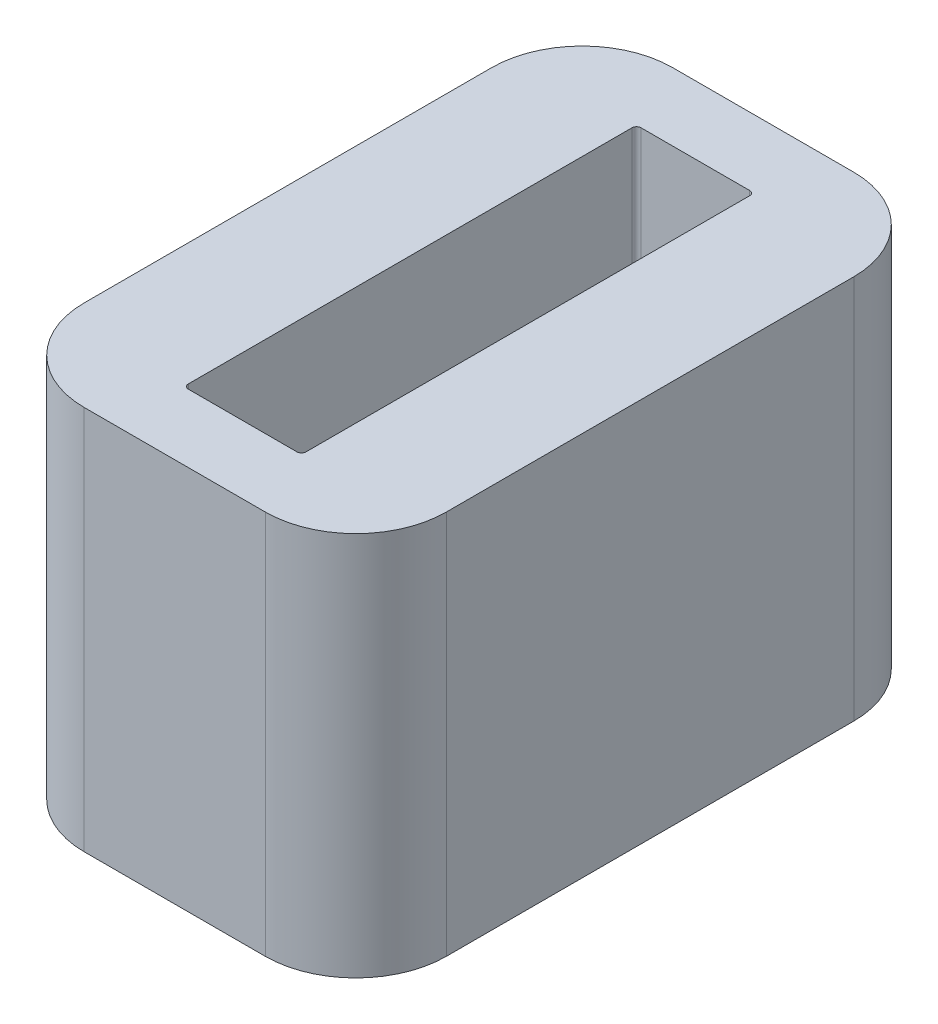
SolidWorks part; units mm, degrees
material "Copper"
ref_plane "Front Plane" through (0, 0, 0) normal (0, 0, 1) x (1, 0, 0)
ref_plane "Top Plane" through (0, 0, 0) normal (0, 1, 0) x (1, 0, 0)
ref_plane "Right Plane" through (0, 0, 0) normal (1, 0, 0) x (0, 0, -1)
sketch "Sketch1" plane through (0, 97.2795, 0) normal (0, 1, 0) x (1, 0, 0)
  line L0 (92.0978, 84.0094) -> (86.0478, 74.2094) construction
  line L1 (86.0478, 74.2094) -> (92.0978, 74.2094) construction
  line L2 (86.0478, 74.2094) -> (86.0478, 84.0094) construction
  line L3 (86.0478, 84.0094) -> (92.0978, 84.0094) construction
  line L4 (92.0978, 74.2094) -> (92.0978, 84.0094) construction
  line L6 (87.0728, 72.6094) -> (91.0728, 72.6094)
  line L7 (85.0728, 74.6094) -> (85.0728, 83.6094)
  line L8 (87.0728, 85.6094) -> (91.0728, 85.6094)
  line L9 (93.0728, 74.6094) -> (93.0728, 83.6094)
  line L10 (85.0728, 72.6094) -> (93.0728, 85.6094) construction
  line L11 (85.0728, 85.6094) -> (93.0728, 72.6094) construction
  line L12 (87.7728, 74.1094) -> (90.3728, 74.1094)
  line L13 (87.7728, 74.1094) -> (87.7728, 84.1094)
  line L14 (87.7728, 84.1094) -> (90.3728, 84.1094)
  line L15 (90.3728, 74.1094) -> (90.3728, 84.1094)
  line L16 (87.7728, 74.1094) -> (90.3728, 84.1094) construction
  line L17 (87.7728, 84.1094) -> (90.3728, 74.1094) construction
  arc A0 (87.0728, 72.6094) -> (85.0728, 74.6094) centre (87.0728, 74.6094) cw
  arc A1 (91.0728, 72.6094) -> (93.0728, 74.6094) centre (91.0728, 74.6094) ccw
  arc A2 (91.0728, 85.6094) -> (93.0728, 83.6094) centre (91.0728, 83.6094) cw
  arc A3 (85.0728, 83.6094) -> (87.0728, 85.6094) centre (87.0728, 83.6094) cw
  point P7 (89.0728, 79.1094)
  point P23 (89.0728, 79.1094)
  dimension "D3" = 2
  dimension "D1" = 8
  dimension "D2" = 13
  dimension "D4" = 2.6
  dimension "D5" = 10
extrude "Coil" add sketch "Sketch1" against normal blind 8.5 from offset 0.7 offset against normal yes
fillet "Fillet1" radius 0.1 4 edges at (90.3728, 92.3295, -74.1094) (87.7728, 92.3295, -74.1094) (87.7728, 92.3295, -84.1094) (90.3728, 92.3295, -84.1094)
